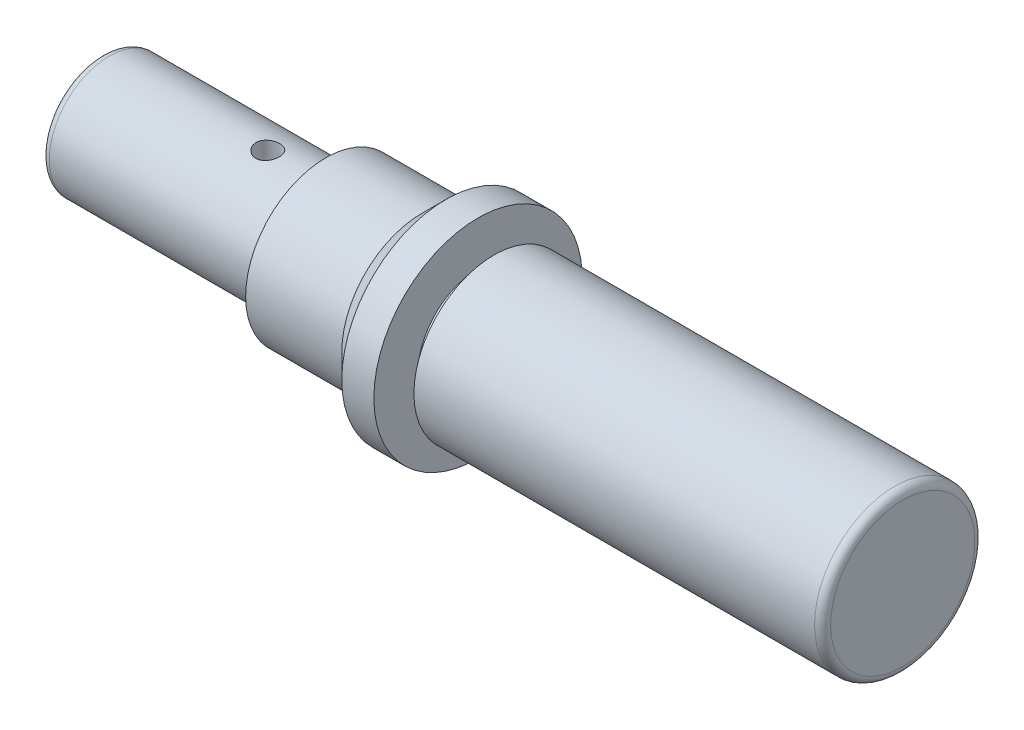
SolidWorks part; units mm, degrees
ref_plane "Front Plane" through (0, 0, 0) normal (0, 0, 1) x (1, 0, 0)
ref_plane "Top Plane" through (0, 0, 0) normal (0, 1, 0) x (1, 0, 0)
ref_plane "Right Plane" through (0, 0, 0) normal (1, 0, 0) x (0, 0, -1)
sketch "Sketch1" plane through (0, 0, 0) normal (0, 0, 1) x (1, 0, 0)
  line L0 (-61.6998, 9.8978) -> (-61.6998, 17.3978)
  line L1 (-61.6998, 17.3978) -> (-33.6998, 17.3978)
  line L2 (-33.6998, 17.3978) -> (-33.6998, 19.8978)
  line L3 (-33.6998, 19.8978) -> (-21.6998, 19.8978)
  line L4 (-21.6998, 19.8978) -> (-18.6998, 22.8978)
  line L5 (-18.6998, 22.8978) -> (-14.6998, 22.8978)
  line L6 (-14.6998, 22.8978) -> (-14.6998, 17.3978)
  line L7 (-14.6998, 17.3978) -> (-12.6998, 17.3978)
  line L8 (-12.6998, 17.3978) -> (-12.6998, 19.8978)
  line L9 (-12.6998, 19.8978) -> (38.3002, 19.8978)
  line L10 (38.3002, 19.8978) -> (38.3002, 9.8978)
  line L11 (-61.6998, 9.8978) -> (41.8177, 9.8978) construction
  line L12 (-61.6998, 9.8978) -> (38.3002, 9.8978)
  dimension "D1" = 7.5
  dimension "D2" = 28
  dimension "D3" = 10
  dimension "D4" = 135
  dimension "D5" = 13
  dimension "D6" = 7
  dimension "D7" = 2
  dimension "D8" = 10
  dimension "D9" = 53
  dimension "D10" = 12
  dimension "D11" = 7.5
revolve "Revolve1" add sketch "Sketch1" angle 360 about L11
fillet "Fillet1" radius 1 2 edges at (38.3002, 9.8978, 10) (-61.6998, 9.8978, 7.5)
hole_wizard "Ø1.0mm Dowel Hole1" positions "3DSketch5" profile "Sketch7" hole size "Ø1.0" standard "ISO" end condition through all
sketch3d "3DSketch5"
  line L0 (-40.6998, 17.3941, 0.2355) -> (-33.6998, 17.3941, 0.2355) construction
  circle A1 centre (-33.6998, 9.8978, 0) radius 7.5 construction
  point P0 (-40.6998, 17.3941, 0.2355)
  point P9 (-41.1998, 9.8978, 0)
  dimension "D1" = 7
sketch "Sketch7" plane through (-40.6998, 17.3941, 0.2355) normal (1, 0, 0) x (0, -0.0314, 0.9995)
  line L0 (0, 0) -> (0, 20.9018)
  line L1 (0, 20.9018) -> (1.5, 20.9018)
  line L2 (1.5, 20.9018) -> (1.5, 0)
  line L5 (1.5, 0) -> (0, 0)
  line L11 (0, -6.35) -> (0, 107.95) construction
  dimension "Thru Hole Dia." = 3
  dimension "Thru Hole Depth" = 20.9018
